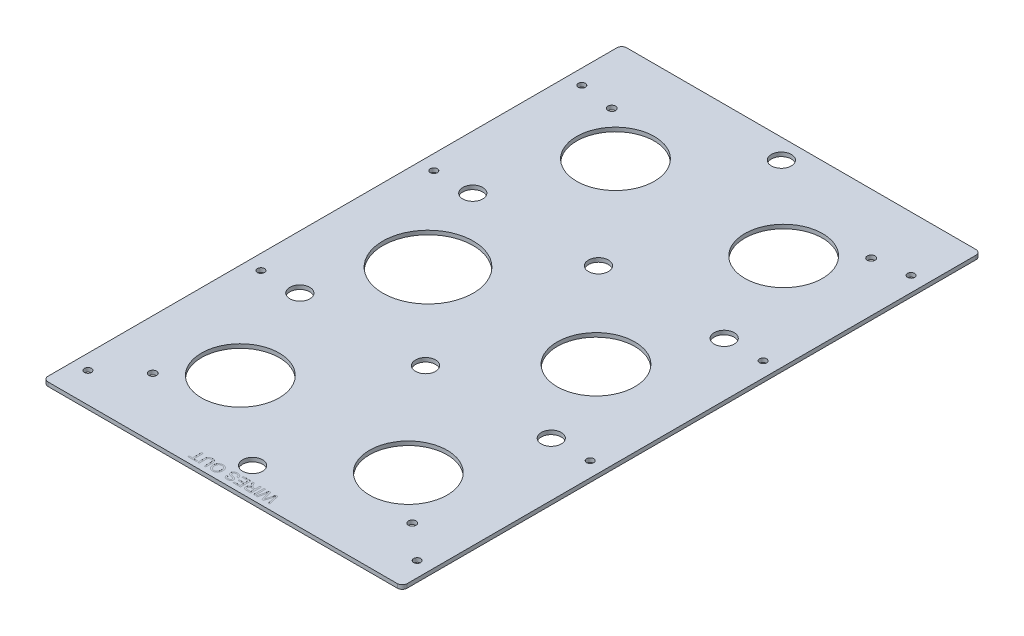
SolidWorks part; units mm, degrees
ref_plane "Front" through (0, 0, 0) normal (0, 0, 1) x (1, 0, 0)
ref_plane "Top" through (0, 0, 0) normal (0, 1, 0) x (1, 0, 0)
ref_plane "Right" through (0, 0, 0) normal (1, 0, 0) x (0, 0, -1)
sketch "Sketch1" plane through (0, 0, 0) normal (0, 1, 0) x (1, 0, 0)
  line L0 (-76.7713, -421.1347) -> (-76.8983, -421.1347) construction
  line L1 (-109.7785, -117.6047) -> (112.4715, -117.6047)
  line L2 (-112.9535, -120.7797) -> (-112.9535, -482.7297)
  line L3 (-109.7785, -485.9047) -> (112.4715, -485.9047)
  line L4 (115.6465, -120.7797) -> (115.6465, -482.7297)
  line L5 (-112.9535, -117.6047) -> (115.6465, -485.9047) construction
  line L6 (-112.9535, -485.9047) -> (115.6465, -117.6047) construction
  line L7 (-71.7672, -281.6904) -> (-32.5753, -321.6904) construction
  line L8 (28.334, -485.9047) -> (112.4715, -485.9047) construction
  line L9 (115.6465, -482.7297) -> (115.6465, -120.7797) construction
  circle A0 centre (54.8643, -421.2633) radius 24.727
  circle A1 centre (54.8643, -301.819) radius 24.727
  circle A2 centre (-52.1713, -421.1347) radius 24.727
  circle A4 centre (-52.1713, -182.3747) radius 24.727
  circle A5 centre (54.8643, -182.3747) radius 24.727
  arc A6 (-47.2145, -445.2302) -> (-49.5629, -396.6734) centre (-52.1713, -421.1347) ccw construction
  arc A7 (-47.2145, -445.2302) -> (-57.128, -397.0393) centre (-52.1713, -421.1347) ccw construction
  arc A8 (115.6465, -120.7797) -> (112.4715, -117.6047) centre (112.4715, -120.7797) ccw
  arc A9 (-112.9535, -120.7797) -> (-109.7785, -117.6047) centre (-109.7785, -120.7797) cw
  arc A10 (-112.9535, -482.7297) -> (-109.7785, -485.9047) centre (-109.7785, -482.7297) ccw
  arc A11 (112.4715, -485.9047) -> (115.6465, -482.7297) centre (112.4715, -482.7297) ccw
  circle A12 centre (-52.1713, -301.6904) radius 28.7693
  circle A13 centre (-78.6635, -356.7838) radius 2.2479 construction
  circle A14 centre (-78.6635, -356.7838) radius 2.2479 construction
  circle A15 centre (1.3465, -356.7881) radius 2.2479 construction
  circle A16 centre (1.3465, -356.7881) radius 2.2479 construction
  circle A17 centre (81.3565, -356.7838) radius 2.2479 construction
  circle A18 centre (81.3565, -356.7838) radius 2.2479 construction
  circle A19 centre (81.3565, -246.7256) radius 2.2479 construction
  circle A20 centre (81.3565, -246.7256) radius 2.2479 construction
  circle A21 centre (1.3465, -246.7214) radius 2.2479 construction
  circle A22 centre (1.3465, -246.7214) radius 2.2479 construction
  circle A23 centre (-78.6635, -246.7256) radius 2.2479 construction
  circle A24 centre (-78.6635, -246.7256) radius 2.2479 construction
  circle A25 centre (1.3465, -130.3047) radius 2.2479 construction
  circle A26 centre (1.3465, -130.3047) radius 2.2479 construction
  circle A27 centre (1.3465, -466.8547) radius 2.2479 construction
  circle A28 centre (1.3465, -466.8547) radius 2.2479 construction
  circle A29 centre (1.3465, -466.8547) radius 6.35
  circle A30 centre (81.3565, -356.7838) radius 6.35
  circle A31 centre (1.3465, -356.7881) radius 6.35
  circle A32 centre (-78.6635, -356.7838) radius 6.35
  circle A33 centre (81.3565, -246.7256) radius 6.35
  circle A34 centre (1.3465, -246.7214) radius 6.35
  circle A35 centre (-78.6635, -246.7256) radius 6.35
  circle A36 centre (1.3465, -130.3047) radius 6.35
  circle A37 centre (83.8965, -155.7047) radius 2.4575 construction
  circle A38 centre (83.8965, -155.7047) radius 2.4575
  circle A39 centre (-81.2035, -155.7047) radius 2.4575 construction
  circle A40 centre (-81.2035, -155.7047) radius 2.4575
  circle A41 centre (-81.2035, -447.8047) radius 2.4575 construction
  circle A42 centre (-81.2035, -447.8047) radius 2.4575
  circle A43 centre (83.8965, -447.8047) radius 2.4575 construction
  circle A44 centre (83.8965, -447.8047) radius 2.4575
  circle A45 centre (-103.4285, -152.5297) radius 2.2479 construction
  circle A46 centre (-103.4285, -152.5297) radius 2.2479
  circle A47 centre (-103.4285, -246.7214) radius 2.2479 construction
  circle A48 centre (-103.4285, -246.7214) radius 2.2479
  circle A49 centre (106.1215, -152.5297) radius 2.2479 construction
  circle A50 centre (106.1215, -152.5297) radius 2.2479
  circle A51 centre (106.1215, -246.7214) radius 2.2479 construction
  circle A52 centre (106.1215, -246.7214) radius 2.2479
  circle A53 centre (106.1215, -356.7881) radius 2.2479 construction
  circle A54 centre (106.1215, -356.7881) radius 2.2479
  circle A55 centre (-103.4285, -356.7881) radius 2.2479 construction
  circle A56 centre (-103.4285, -356.7881) radius 2.2479
  circle A57 centre (-103.4285, -466.8547) radius 2.2479 construction
  circle A58 centre (-103.4285, -466.8547) radius 2.2479
  circle A59 centre (106.1215, -466.8547) radius 2.2479 construction
  circle A60 centre (106.1215, -466.8547) radius 2.2479
  point P0 (1.3465, -301.7547)
  dimension "D3" = 0.127
  dimension "D4" = 3.175
  dimension "D5" = 12.7
  dimension "D1" = 228.6
  dimension "D2" = 368.3
extrude "Boss-Extrude1" add sketch "Sketch1" along normal blind 2.54
sketch "Sketch2" plane through (0, 2.54, 0) normal (0, 1, 0) x (1, 0, 0)
  line L0 (28.1392, -475.9047) -> (28.1392, -485.9047) construction
  line L2 (28.1392, -475.9047) -> (-22.6608, -475.9047) construction
  line L3 (-109.7785, -485.9047) -> (112.4715, -485.9047) construction
  line L4 (115.6465, -482.7297) -> (115.6465, -120.7797) construction
  text T0 "WIRES OUT" font "Arial" height in points 26
  dimension "D1" = 10
  dimension "D2" = 50.8
  dimension "D3" = 87.5074
extrude "Cut-Extrude2" cut sketch "Sketch2" against normal blind 0.0254
